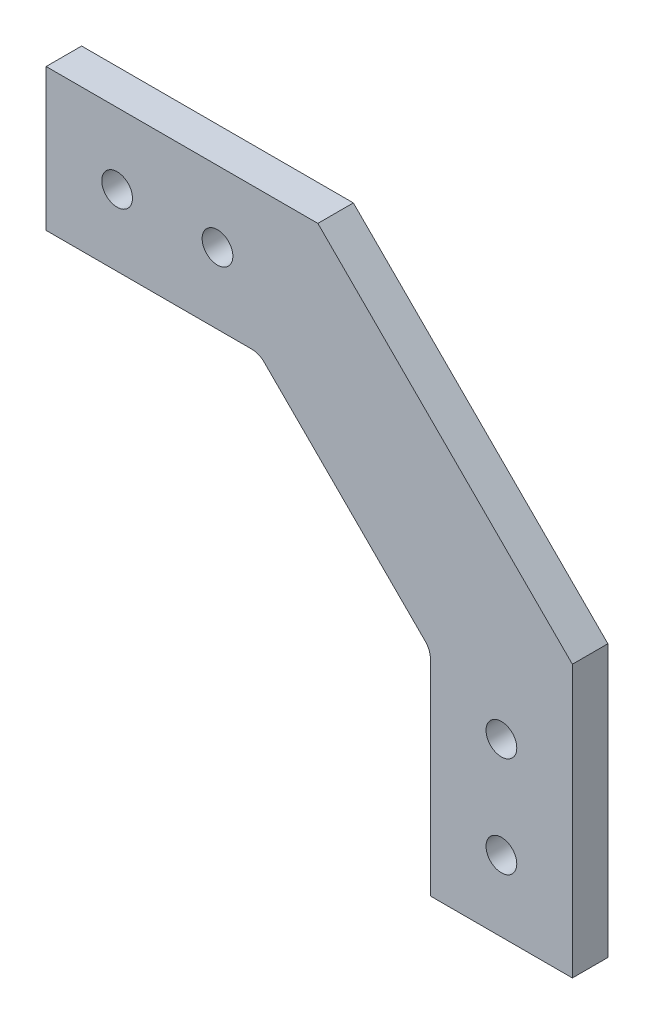
SolidWorks part; units mm, degrees
material "6061-T6 (SS)"
ref_plane "Front" through (0, 0, 0) normal (0, 0, 1) x (1, 0, 0)
ref_plane "Top" through (0, 0, 0) normal (0, 1, 0) x (1, 0, 0)
ref_plane "Right" through (0, 0, 0) normal (1, 0, 0) x (0, 0, -1)
sketch "Sketch4" plane through (-292.1, 0, 0) normal (0, 0, 1) x (1, 0, 0)
  line L0 (292.1, 63.5) -> (292.1, 0)
  line L1 (342.1, 0) -> (242.1, 0) construction
  line L2 (292.1, 63.5) -> (254, 101.6)
  line L4 (254, 101.6) -> (-254, 101.6)
  line L5 (292.1, 0) -> (-292.1, 0) construction
  line L6 (-254, 101.6) -> (-292.1, 63.5)
  line L7 (-292.1, 63.5) -> (-292.1, -25.4)
  dimension "D1" = 90
sketch "Sketch1" plane through (0, 0, 0) normal (0, 0, 1) x (1, 0, 0)
  line L0 (-12.7, 29.0295) -> (-12.7, 58.2395)
  line L6 (-12.7, 58.2395) -> (-43.3605, 88.9)
  line L7 (-43.3605, 88.9) -> (-81.4605, 88.9)
  line L8 (-81.4605, 88.9) -> (-81.4605, 114.3)
  line L9 (-81.4605, 114.3) -> (-32.8395, 114.3)
  line L10 (-32.8395, 114.3) -> (12.7, 68.7605)
  line L11 (12.7, 68.7605) -> (12.7, 37.9195)
  line L12 (-12.7, 29.0295) -> (-12.7, 0) construction
  line L13 (0, 63.5) -> (-38.1, 101.6) construction
  line L14 (-38.1, 101.6) -> (-546.1, 101.6) construction
  line L15 (12.7, 37.9195) -> (-12.7, 37.9195) construction
  line L16 (-12.7, 37.9195) -> (-12.7, 58.2395) construction
  line L17 (12.7, 29.0295) -> (12.7, 20.1395)
  line L18 (12.7, 20.1395) -> (-12.7, 20.1395)
  line L19 (-12.7, 20.1395) -> (-12.7, 29.0295)
  line L20 (12.7, 29.0295) -> (-12.7, 29.0295) construction
  line L21 (12.7, 37.9195) -> (12.7, 29.0295)
  line L22 (0, 20.1395) -> (0, 0) construction
  line L23 (0, 0) -> (-584.2, 0) construction
  dimension "D1" = 25.4
  dimension "D2" = 8.89
  dimension "D3" = 38.1
  dimension "D4" = 8.89
  dimension "D5" = 12.7
  dimension "D6" = 12.7
  dimension "D7" = 12.7
  dimension "D8" = 12.7
  dimension "D9" = 38.1
extrude "Boss-Extrude1" add sketch "Sketch1" along normal blind 6.35
fillet "Fillet1" radius 3.175 2 edges at (-43.3605, 88.9, 3.175) (-12.7, 58.2395, 3.175)
hole_wizard "M5 Clearance Hole1" positions "Sketch2" profile "Sketch3" hole size "M5" standard "ANSI Metric"
sketch "Sketch2" plane through (0, 0, 6.35) normal (0, 0, 1) x (1, 0, 0)
  line L14 (-81.4605, 114.3) -> (-68.7605, 101.6) construction
  line L15 (-68.7605, 101.6) -> (-81.4605, 88.9) construction
  line L17 (-68.7605, 101.6) -> (-50.8, 101.6) construction
  line L22 (12.7, 20.1395) -> (0, 32.8395) construction
  line L23 (0, 32.8395) -> (-12.7, 20.1395) construction
  line L25 (0, 32.8395) -> (0, 50.8) construction
  point P0 (0, 50.8)
  point P48 (-50.8, 101.6)
  point P50 (-68.7605, 101.6)
  point P87 (0, 32.8395)
  dimension "D4" = 12.7
sketch "Sketch3" plane through (0, 50.8, 6.35) normal (1, 0, 0) x (0, -1, 0)
  line L0 (0, 0) -> (0, 20.4024)
  line L1 (0, 20.4024) -> (2.75, 18.75)
  line L2 (2.75, 18.75) -> (2.75, 0)
  line L5 (2.75, 0) -> (0, 0)
  line L10 (0, 20.4024) -> (-2.75, 18.75) construction
  line L11 (0, -6.35) -> (0, 107.95) construction
  dimension "Hole Dia." = 5.5
  dimension "Hole Depth" = 18.75
  dimension "Drill Angle" = 118
